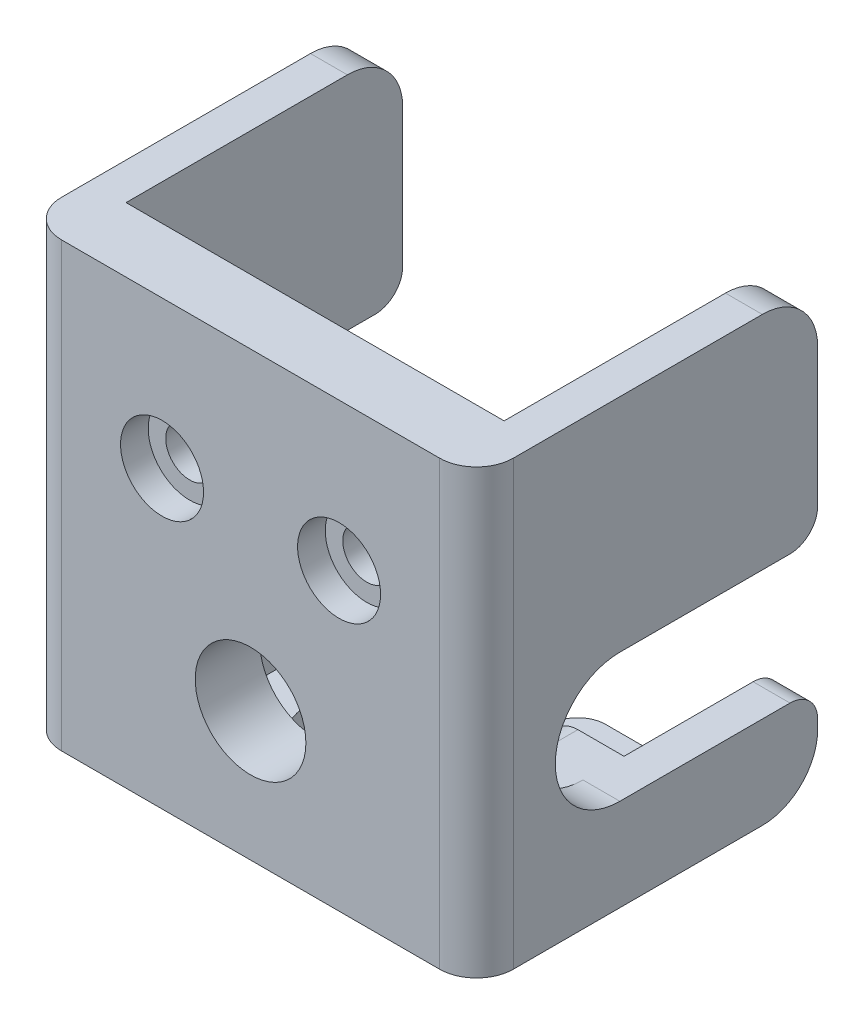
SolidWorks part; units mm, degrees
ref_plane "Front Plane" through (0, 0, 0) normal (0, 0, 1) x (1, 0, 0)
ref_plane "Top Plane" through (0, 0, 0) normal (0, 1, 0) x (1, 0, 0)
ref_plane "Right Plane" through (0, 0, 0) normal (1, 0, 0) x (0, 0, -1)
sketch "Sketch1" plane through (0, 0, 0) normal (0, 0, 1) x (1, 0, 0)
  line L0 (-10.25, 13) -> (10.25, 13)
  line L1 (-10.25, 13) -> (-10.25, -11)
  line L2 (-10.25, -11) -> (10.25, -11)
  line L3 (10.25, 13) -> (10.25, -11)
  line L4 (-4.8, 5) -> (4.8, 5) construction
  line L5 (0, -4) -> (0, -11) construction
  line L6 (0, 13) -> (0, 5) construction
  line L7 (0, 5) -> (0, 0) construction
  line L8 (0, 0) -> (0, -4) construction
  circle A1 centre (-4.8, 5) radius 1.3
  circle A2 centre (4.8, 5) radius 1.3
  circle A3 centre (0, -4) radius 3
  point P14 (0, 5)
  dimension "D3" = 2.6
  dimension "D4" = 6
  dimension "D1" = 24
  dimension "D2" = 20.5
  dimension "D5" = 7
  dimension "D6" = 8
  dimension "D7" = 9.6
  dimension "D8" = 4
extrude "Boss-Extrude1" add sketch "Sketch1" along normal blind 3.5
sketch "Sketch2" plane through (0, -11, 0) normal (0, -1, 0) x (-1, 0, 0)
  line L1 (10.25, -3.5) -> (12.25, -3.5)
  line L2 (10.25, -3.5) -> (10.25, 15)
  line L3 (10.25, 15) -> (12.25, 15)
  line L4 (12.25, -3.5) -> (12.25, 15)
  line L5 (-10.25, -3.5) -> (-12.25, -3.5)
  line L6 (-10.25, -3.5) -> (-10.25, 15)
  line L7 (-10.25, 15) -> (-12.25, 15)
  line L8 (-12.25, -3.5) -> (-12.25, 15)
  dimension "D1" = 2
  dimension "D2" = 18.5
extrude "Boss-Extrude2" add sketch "Sketch2" against normal up to vertex (24 mm away) up to point (10.25, 13, 0)
sketch "Sketch3" plane through (0, -11, 0) normal (0, -1, 0) x (1, 0, 0)
  line L0 (0, 3.5) -> (0, 0) construction
  line L5 (-12.25, 3.5) -> (12.25, 3.5) construction
  line L6 (0, 0) -> (0, -15.097) construction
  line L11 (-3.75, -10.5) -> (3.75, -10.5) construction
  line L12 (-10.25, 0) -> (-3.75, 0)
  line L13 (-10.25, 0) -> (-10.25, -10.5)
  line L14 (-10.25, -10.5) -> (-3.75, -10.5)
  line L15 (-3.75, 0) -> (-3.75, -10.5)
  line L16 (10.25, 0) -> (3.75, 0)
  line L17 (10.25, 0) -> (10.25, -10.5)
  line L18 (10.25, -10.5) -> (3.75, -10.5)
  line L19 (3.75, 0) -> (3.75, -10.5)
  point P15 (0, -10.5)
  dimension "D1" = 10.5
  dimension "D3" = 7.5
extrude "Boss-Extrude3" add sketch "Sketch3" against normal blind 2
fillet "Fillet1" radius 3.5 2 edges at (3.75, -10, 0) (-3.75, -10, 0)
fillet "Fillet2" radius 2 2 edges at (-12.25, 1, 3.5) (12.25, 1, 3.5)
sketch "Sketch4" plane through (0, 0, 3.5) normal (0, 0, 1) x (1, 0, 0)
  circle A0 centre (-4.8, 5) radius 2.25
  circle A1 centre (4.8, 5) radius 2.25
  dimension "D1" = 4.5
extrude "Cut-Extrude1" cut sketch "Sketch4" against normal blind 1.5
fillet "Fillet4" radius 3 3 edges at (11.25, 13, -15) (-11.25, 13, -15) (11.25, -11, -15)
sketch "Sketch7" plane through (12.25, 0, 0) normal (1, 0, 0) x (0, 0, -1)
  line L0 (-1.0366, -11) -> (-1.0366, -2.5) construction
  line L1 (12, -11) -> (-1.5, -11) construction
  line L2 (0.7746, -2.5) -> (-1.0366, -2.5) construction
  line L4 (4.2746, -2.5) -> (16.1029, -2.5) construction
  line L5 (4.2746, 1) -> (16.1029, 1)
  line L6 (4.2746, -6) -> (16.1029, -6)
  arc A0 (4.2746, 1) -> (4.2746, -6) centre (4.2746, -2.5) ccw
  arc A1 (16.1029, -6) -> (16.1029, 1) centre (16.1029, -2.5) ccw
  point P9 (10.1887, -2.5)
  dimension "D1" = 3.5
  dimension "D2" = 8.5
extrude "Cut-Extrude4" cut sketch "Sketch7" against normal through all
fillet "Fillet5" radius 1.5 1 edges at (-11.25, 1, -15)
sketch "Sketch9" plane through (0, 0, 0) normal (0, 0, -1) x (-1, 0, 0)
  line L1 (-10.25, -9) -> (-6.25, -9)
  line L2 (-10.25, -9) -> (-10.25, -6)
  line L3 (-10.25, -6) -> (-6.25, -6)
  line L4 (-6.25, -9) -> (-6.25, -6)
  line L5 (10.25, -9) -> (6.25, -9)
  line L6 (10.25, -9) -> (10.25, -6)
  line L7 (10.25, -6) -> (6.25, -6)
  line L8 (6.25, -9) -> (6.25, -6)
  dimension "D1" = 4
  dimension "D2" = 3
extrude "Boss-Extrude4" add sketch "Sketch9" along normal blind 6.5
sketch "Sketch10" plane through (12.25, 0, 0) normal (1, 0, 0) x (0, 0, -1)
  line L0 (15, -6) -> (4.2746, -6)
  line L1 (15, -6) -> (15, 1)
  line L2 (15, 1) -> (4.2746, 1)
  line L3 (15, 1) -> (4.2746, 1) construction
  arc A0 (4.2746, 1) -> (4.2746, -6) centre (4.2746, -2.5) ccw construction
  arc A1 (4.2746, 1) -> (4.2746, -6) centre (4.2746, -2.5) ccw
extrude "Boss-Extrude5" [suppressed] add sketch "Sketch10" against normal up to vertex up to point (10.25, 1, -15)
fillet "Fillet6" radius 1.5 7 edges at (-6.25, -6, -3.25) (6.25, -6, -3.25) (10.25, -10, -10.5) (-3.75, -10, -10.5) (3.75, -10, -10.5) (11.25, 1, -15) (11.25, -6, -15)
sketch "Sketch11" plane through (0, 0, -15) normal (0, 0, -1) x (-1, 0, 0)
  line L1 (12.25, -6) -> (10.25, -6)
  line L2 (12.25, -6) -> (12.25, -11)
  line L3 (12.25, -11) -> (10.25, -11)
  line L4 (10.25, -6) -> (10.25, -11)
extrude "Cut-Extrude5" cut sketch "Sketch11" against normal blind 10
fillet "Fillet7" radius 1.5 2 edges at (-10.25, -10, -10.5) (-12.25, -8.5, -5)
